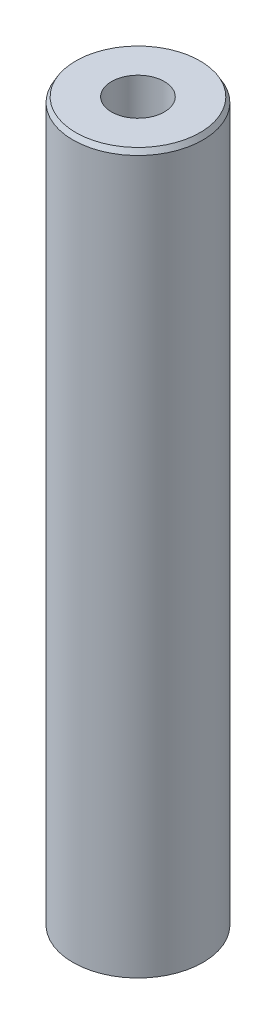
SolidWorks part; units mm, degrees
ref_plane "Front Plane" through (0, 0, 0) normal (0, 0, 1) x (1, 0, 0)
ref_plane "Top Plane" through (0, 0, 0) normal (0, 1, 0) x (1, 0, 0)
ref_plane "Right Plane" through (0, 0, 0) normal (1, 0, 0) x (0, 0, -1)
sketch "Sketch1" plane through (0, 0, 0) normal (0, 1, 0) x (1, 0, 0)
  circle A0 centre (0, 0) radius 10
  dimension "SHAFT_OD" = 20
extrude "Boss-Extrude1" add sketch "Sketch1" along normal blind 110.7802
sketch "Sketch2" plane through (0, 0, 0) normal (0, 1, 0) x (1, 0, 0)
  circle A0 centre (0, 0) radius 4.0625
  dimension "BORE_D" = 8.1251
extrude "Cut-Extrude1" cut sketch "Sketch2" along normal through all
chamfer "Chamfer1" distance 0.7642 angle 30 2 edges at (0, 110.7802, 10) (0, 0, 10) first distance on face at (0, 110.7802, 10) first distance on face at (0, 0, 4.0625)
